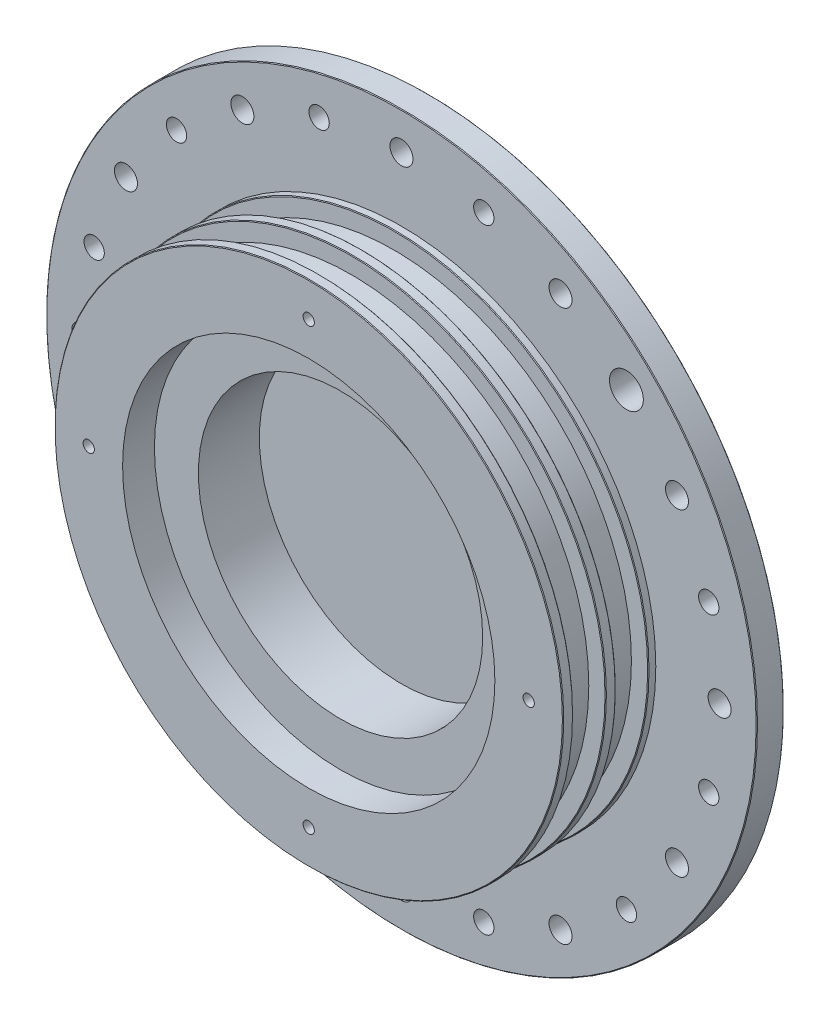
SolidWorks part; units mm, degrees
other "Marquage1"
sketch "Esquisse22" plane through (-100, 100, -114.225) normal (-0.6969, 0.6451, 0.3132) x (0.5706, 0.7634, -0.3027)
sketch "Esquisse26" plane through (-110, 110, -114.225) normal (-0.6969, 0.6451, 0.3132) x (0.5706, 0.7634, -0.3027)
sketch "Esquisse28" plane through (-110, 110, -114.225) normal (-0.6969, 0.6451, 0.3132) x (0.5706, 0.7634, -0.3027)
sketch "Esquisse31" plane through (-110, 110, -114.225) normal (-0.6969, 0.6451, 0.3132) x (0.5706, 0.7634, -0.3027)
sketch "Esquisse32" plane through (-100, 100, -114.225) normal (-0.6969, 0.6451, 0.3132) x (0.5706, 0.7634, -0.3027)
material "AISI 316 Barre d'acier inoxydable recuit (SS)"
ref_plane "Plan de face" through (0, 0, 0) normal (0, 0, 1) x (1, 0, 0)
ref_plane "Plan de dessus" through (0, 0, 0) normal (0, 1, 0) x (1, 0, 0)
ref_plane "Plan de droite" through (0, 0, 0) normal (1, 0, 0) x (0, 0, -1)
sketch "Esquisse1" plane through (0, 0, 0) normal (0, 1, 0) x (1, 0, 0)
  line L0 (87.5, 35.4) -> (0, 35.4)
  line L1 (0, 35.4) -> (0, 0)
  line L2 (0, 0) -> (75.15, 0)
  line L3 (75.15, 0) -> (75.15, 3)
  line L4 (75.15, 3) -> (70.15, 3)
  line L5 (70.15, 3) -> (70.15, 12.6)
  line L6 (70.15, 12.6) -> (75.15, 12.6)
  line L7 (75.15, 12.6) -> (75.15, 15.6)
  line L8 (75.15, 15.6) -> (70.15, 15.6)
  line L9 (70.15, 15.6) -> (70.15, 25.2)
  line L10 (70.15, 25.2) -> (75.15, 25.2)
  line L11 (75.15, 25.2) -> (75.15, 27.4)
  line L12 (75.15, 27.4) -> (87.5, 27.4)
  line L13 (87.5, 27.4) -> (87.5, 35.4)
  line L14 (0, 35.4) -> (0, 0) construction
  dimension "D1" = 8
  dimension "D2" = 2.2
  dimension "D3" = 9.6
  dimension "D4" = 3
  dimension "D5" = 9.6
  dimension "D6" = 3
  dimension "D7" = 5
  dimension "D8" = 75.15
  dimension "D9" = 87.5
revolve "Révolution1" add sketch "Esquisse1" angle 360 about L14 reverse direction yes
hole_wizard "Diamètre du perçage Ø9.0 (9)1" positions "Esquisse3" profile "Esquisse2" hole size "Ø9.0" standard "Ansi Metric"
sketch "Esquisse3" plane through (0, 0, -27.4) normal (0, 0, 1) x (1, 0, 0)
  point P0 (-87.5, 0)
  point P1 (0, 87.5)
  point P2 (0, -87.5)
  point P3 (87.5, 0)
sketch "Esquisse2" plane through (-87.5, 0, -27.4) normal (1, 0, 0) x (0, -1, 0)
  line L0 (0, 0) -> (0, 3)
  line L1 (0, 3) -> (4.5, 3)
  line L2 (4.5, 3) -> (4.5, 0)
  line L5 (4.5, 0) -> (0, 0)
  line L10 (0, 3) -> (-4.5, 3) construction
  line L11 (0, -6.35) -> (0, 107.95) construction
  dimension "Diamètre du perçage" = 9
  dimension "Profondeur du perçage" = 3
  dimension "Angle de pointe" = 180
hole_wizard "Dégagement M31" positions "Esquisse5" profile "Esquisse4" hole size "M3" standard "Ansi Metric"
sketch "Esquisse5" plane through (0, 0, 0) normal (0, 0, 1) x (1, 0, 0)
  point P0 (-65, 0)
  point P1 (65, 0)
  point P2 (0, 65)
  point P3 (0, -65)
sketch "Esquisse4" plane through (-65, 0, 0) normal (1, 0, 0) x (0, -1, 0)
  line L0 (0, 0) -> (0, 17.001)
  line L1 (0, 17.001) -> (1.666, 16)
  line L2 (1.666, 16) -> (1.666, 0)
  line L5 (1.666, 0) -> (0, 0)
  line L10 (0, 17.001) -> (-1.666, 16) construction
  line L11 (0, -6.35) -> (0, 107.95) construction
  dimension "Diamètre du perçage" = 3.332
  dimension "Profondeur du perçage" = 16
  dimension "Angle de pointe" = 118
hole_wizard "Dégagement M1001" positions "Esquisse7" profile "Esquisse6" hole size "M100" standard "Ansi Metric"
sketch "Esquisse7" plane through (0, 0, 0) normal (0, 0, 1) x (1, 0, 0)
  point P0 (0, 0)
sketch "Esquisse6" plane through (0, 0, 0) normal (1, 0, 0) x (0, -1, 0)
  line L0 (0, 0) -> (0, 27.4)
  line L1 (0, 27.4) -> (55, 27.4)
  line L2 (55, 27.4) -> (55, 0)
  line L5 (55, 0) -> (0, 0)
  line L10 (0, 27.4) -> (-55, 27.4) construction
  line L11 (0, -6.35) -> (0, 107.95) construction
  dimension "Diamètre du perçage" = 110
  dimension "Profondeur du perçage" = 27.4
  dimension "Angle de pointe" = 180
sketch "Esquisse8" plane through (0, 0, -35.4) normal (0, 0, -1) x (-1, 0, 0)
  line L0 (0, 0) -> (0, -108.9201) construction
  circle A0 centre (0, 0) radius 108.9201 construction
  circle A1 centre (0, 0) radius 105
  circle A2 centre (0, 0) radius 77.5
  circle A3 centre (0, 0) radius 87.5 construction
  dimension "D2" = 10
  dimension "D1" = 210
extrude "Boss.-Extru.1" add sketch "Esquisse8" against normal blind 8
ref_plane "Plan1" through (0, -105, 0) normal (0, -1, 0) x (-1, 0, 0)
sketch "Esquisse9" plane through (0, 0, -35.4) normal (0, 0, 1) x (1, 0, 0)
  line L0 (0, -50) -> (0, 0) construction
  circle A0 centre (0, -50) radius 3.4
  circle A17 centre (0, -94) radius 3.4
  circle A18 centre (-25, -43.3013) radius 3.4
  circle A19 centre (-47, -81.4064) radius 3.4
  circle A20 centre (-43.3013, -25) radius 3.4
  circle A21 centre (-81.4064, -47) radius 3.4
  circle A22 centre (-50, 0) radius 3.4
  circle A23 centre (-94, 0) radius 3.4
  circle A24 centre (-43.3013, 25) radius 3.4
  circle A25 centre (-81.4064, 47) radius 3.4
  circle A26 centre (-25, 43.3013) radius 3.4
  circle A27 centre (-47, 81.4064) radius 3.4
  circle A28 centre (0, 50) radius 3.4
  circle A29 centre (0, 94) radius 3.4
  circle A30 centre (25, 43.3013) radius 3.4
  circle A31 centre (47, 81.4064) radius 3.4
  circle A32 centre (43.3013, 25) radius 3.4
  circle A33 centre (81.4064, 47) radius 3.4
  circle A34 centre (50, 0) radius 3.4
  circle A35 centre (94, 0) radius 3.4
  circle A36 centre (43.3013, -25) radius 3.4
  circle A37 centre (81.4064, -47) radius 3.4
  circle A38 centre (25, -43.3013) radius 3.4
  circle A39 centre (47, -81.4064) radius 3.4
  point P17 (0, 0)
  point P28 (0, 0)
  point P31 (0, 0)
  point P55 (0, 0)
  dimension "D1" = 6.8
  dimension "D3" = 94
  dimension "D2" = 50
extrude "Enlèv. mat.-Extru.1" cut sketch "Esquisse9" along normal blind 20
sketch "Esquisse24" plane through (0, 0, -35.4) normal (0, 0, -1) x (-1, 0, 0)
  line L0 (28.0621, 104.7291) -> (0, 0) construction
  line L1 (-54.2118, 93.8976) -> (0, 0) construction
  line L2 (0, 0) -> (0, 94) construction
  line L3 (0, 0) -> (-66.468, 66.468) construction
  circle A0 centre (-47, 81.4064) radius 5 construction
  circle A1 centre (24.329, 90.797) radius 3
  circle A2 centre (66.468, 66.468) radius 3
  circle A3 centre (90.797, 24.329) radius 3
  circle A4 centre (90.797, -24.329) radius 3
  circle A5 centre (-14, 24.2487) radius 5.1
  circle A6 centre (7.2469, 27.0459) radius 5.1
  circle A7 centre (24.2487, 14) radius 5.1
  circle A8 centre (27.0459, -7.2469) radius 5.1
  circle A9 centre (14, -24.2487) radius 5.1
  circle A10 centre (-7.2469, -27.0459) radius 5.1
  circle A11 centre (-24.2487, -14) radius 5.1
  circle A12 centre (-27.0459, 7.2469) radius 5.1
  circle A13 centre (-66.468, 66.468) radius 5
  circle A14 centre (66.468, -66.468) radius 3
  circle A15 centre (24.329, -90.797) radius 3
  circle A16 centre (-24.329, -90.797) radius 3
  circle A17 centre (-66.468, -66.468) radius 3
  circle A18 centre (-90.797, -24.329) radius 3
  circle A19 centre (-90.797, 24.329) radius 3
  circle A20 centre (-66.468, 66.468) radius 3 construction
  circle A21 centre (-24.329, 90.797) radius 3
  circle A22 centre (0, 0) radius 82.55 construction
  circle A23 centre (-66.468, 66.468) radius 8 construction
  circle A24 centre (0, 0) radius 5.1
  point P19 (0, 0)
  point P36 (0, 0)
  dimension "D1" = 6
  dimension "D3" = 10
  dimension "D6" = 10.2
  dimension "D11" = 15
  dimension "D12" = 10
  dimension "D14" = 165.1
  dimension "D15" = 16
  dimension "D2" = 94
  dimension "D4" = 94
  dimension "D7" = 28
  dimension "D9" = 45
  dimension "D10" = 15
  dimension "D13" = 94
  dimension "D5" = 12
  dimension "D8" = 8
extrude "Enlèv. mat.-Extru.15" cut sketch "Esquisse24" against normal through all and the other way through all
chamfer "Chanfrein1" distance 0.2 angle 45 7 edges at (75.15, 0, -25.2) (75.15, 0, -3) (75.15, 0, -12.6) (75.15, 0, -15.6) (-105, 0, -35.4) (-105, 0, -27.4) (75.15, 0, 0)
sketch "Esquisse25" plane through (0, 0, -35.4) normal (0, 0, -1) x (-1, 0, 0)
  line L4 (0, 0) -> (-27.0459, 7.2469) construction
  line L5 (0, 0) -> (-50, 0) construction
  line L8 (-10.1, 3.1378) -> (-10.1, -3.1378)
  line L13 (10.1, 3.1378) -> (10.1, -3.1378)
  arc A1 (-10.1, 4.6043) -> (10.1, 4.6043) centre (0, 0) cw construction
  arc A2 (10.1, -4.6043) -> (-10.1, -4.6043) centre (0, 0) cw construction
  arc A3 (10.1, 3.1378) -> (9.4049, 5.8956) centre (7.191, 3.8711) ccw
  arc A4 (-10.1, 3.1378) -> (-9.4049, 5.8956) centre (-7.191, 3.8711) cw
  arc A5 (10.1, -3.1378) -> (9.4049, -5.8956) centre (7.191, -3.8711) cw
  arc A6 (-10.1, -3.1378) -> (-9.4049, -5.8956) centre (-7.191, -3.8711) ccw
  arc A7 (-9.4049, 5.8956) -> (9.4049, 5.8956) centre (0, 0) cw
  arc A8 (-9.4049, -5.8956) -> (9.4049, -5.8956) centre (0, 0) ccw
  point P5 (0, 0)
  point P19 (10.1, 4.6043)
  line B0 (-24.9287, -1.7061) -> (-33.3561, 0.552) construction
  line B1 (-33.3561, 0.552) -> (-29.1632, 16.2) construction
  line B2 (-29.1632, 16.2) -> (-20.7358, 13.9419) construction
  line B3 (-20.7358, 13.9419) -> (-24.9287, -1.7061) construction
  line B4 (-22.8322, 6.1179) -> (-31.2596, 8.376) construction
  line B5 (-27.0459, 7.2469) -> (-29.1424, -0.5771) construction
  line B6 (-22.5347, 14.4239) -> (-27.3643, 15.718)
  line B7 (-26.7275, -1.2241) -> (-31.5572, 0.07)
  arc B8 (-33.3561, 0.552) -> (-29.1632, 16.2) centre (-27.0459, 7.2469) cw construction
  arc B9 (-24.9287, -1.7061) -> (-20.7358, 13.9419) centre (-27.0459, 7.2469) ccw construction
  arc B10 (-22.8033, -0.9164) -> (-19.29, 12.1953) centre (-27.0459, 7.2469) ccw
  arc B11 (-19.29, 12.1953) -> (-19.4952, 12.5745) centre (-16.7609, 13.8089) cw
  arc B12 (-19.4952, 12.5745) -> (-21.9939, 14.3309) centre (-22.2295, 11.3402) ccw
  arc B13 (-21.9939, 14.3309) -> (-22.5347, 14.4239) centre (-21.7582, 17.3217) cw
  arc B14 (-27.8791, 15.9079) -> (-27.3643, 15.718) centre (-26.5878, 18.6158) ccw
  arc B15 (-30.9212, 15.6361) -> (-27.8791, 15.9079) centre (-29.1704, 13.2) cw
  arc B16 (-31.2885, 15.4103) -> (-30.9212, 15.6361) centre (-32.672, 18.0722) ccw
  arc B17 (-34.8018, 2.2986) -> (-31.2885, 15.4103) centre (-27.0459, 7.2469) cw
  arc B18 (-34.8018, 2.2986) -> (-34.5966, 1.9193) centre (-37.3309, 0.685) cw
  arc B19 (-34.5966, 1.9193) -> (-32.098, 0.1629) centre (-31.8623, 3.1537) ccw
  arc B20 (-32.098, 0.1629) -> (-31.5572, 0.07) centre (-32.3336, -2.8278) cw
  arc B21 (-26.2127, -1.414) -> (-26.7275, -1.2241) centre (-27.504, -4.1219) ccw
  arc B22 (-23.1707, -1.1423) -> (-26.2127, -1.414) centre (-24.9215, 1.2939) cw
  arc B23 (-22.8033, -0.9164) -> (-23.1707, -1.1423) centre (-21.4198, -3.5784) ccw
  line B24 (-5.7352, 26.1336) -> (-8.2352, 30.4638)
  line B25 (-19.7648, 18.0336) -> (-22.2648, 22.3638)
  arc B26 (-16.7724, 15.4764) -> (-5.0167, 22.2635) centre (-14, 24.2487) ccw
  arc B27 (-5.0167, 22.2635) -> (-4.8937, 22.6768) centre (-2.0874, 21.6161) cw
  arc B28 (-4.8937, 22.6768) -> (-5.4185, 25.6855) centre (-7.6999, 23.7374) ccw
  arc B29 (-5.4185, 25.6855) -> (-5.7352, 26.1336) centre (-3.1371, 27.6336) cw
  arc B30 (-8.4649, 30.9621) -> (-8.2352, 30.4638) centre (-5.6371, 31.9638) ccw
  arc B31 (-10.8082, 32.921) -> (-8.4649, 30.9621) centre (-11.2928, 29.9604) cw
  arc B32 (-11.2276, 33.0211) -> (-10.8082, 32.921) centre (-10.3236, 35.8816) ccw
  arc B33 (-22.9833, 26.2339) -> (-11.2276, 33.0211) centre (-14, 24.2487) cw
  arc B34 (-22.9833, 26.2339) -> (-23.1063, 25.8207) centre (-25.9126, 26.8813) cw
  arc B35 (-23.1063, 25.8207) -> (-22.5815, 22.8119) centre (-20.3001, 24.76) ccw
  arc B36 (-22.5815, 22.8119) -> (-22.2648, 22.3638) centre (-24.8629, 20.8638) cw
  arc B37 (-19.5351, 17.5353) -> (-19.7648, 18.0336) centre (-22.3629, 16.5336) ccw
  arc B38 (-17.1918, 15.5764) -> (-19.5351, 17.5353) centre (-16.7072, 18.537) cw
  arc B39 (-16.7724, 15.4764) -> (-17.1918, 15.5764) centre (-17.6764, 12.6158) ccw
  line B40 (14.4239, 22.5347) -> (15.718, 27.3643)
  line B41 (-1.2241, 26.7275) -> (0.07, 31.5572)
  arc B42 (-0.9164, 22.8033) -> (12.1953, 19.29) centre (7.2469, 27.0459) ccw
  arc B43 (12.1953, 19.29) -> (12.5745, 19.4952) centre (13.8089, 16.7609) cw
  arc B44 (12.5745, 19.4952) -> (14.3309, 21.9939) centre (11.3402, 22.2295) ccw
  arc B45 (14.3309, 21.9939) -> (14.4239, 22.5347) centre (17.3217, 21.7582) cw
  arc B46 (15.9079, 27.8791) -> (15.718, 27.3643) centre (18.6158, 26.5878) ccw
  arc B47 (15.6361, 30.9212) -> (15.9079, 27.8791) centre (13.2, 29.1704) cw
  arc B48 (15.4103, 31.2885) -> (15.6361, 30.9212) centre (18.0722, 32.672) ccw
  arc B49 (2.2986, 34.8018) -> (15.4103, 31.2885) centre (7.2469, 27.0459) cw
  arc B50 (2.2986, 34.8018) -> (1.9193, 34.5966) centre (0.685, 37.3309) cw
  arc B51 (1.9193, 34.5966) -> (0.1629, 32.098) centre (3.1537, 31.8623) ccw
  arc B52 (0.1629, 32.098) -> (0.07, 31.5572) centre (-2.8278, 32.3336) cw
  arc B53 (-1.414, 26.2127) -> (-1.2241, 26.7275) centre (-4.1219, 27.504) ccw
  arc B54 (-1.1423, 23.1707) -> (-1.414, 26.2127) centre (1.2939, 24.9215) cw
  arc B55 (-0.9164, 22.8033) -> (-1.1423, 23.1707) centre (-3.5784, 21.4198) ccw
  line B56 (26.1336, 5.7352) -> (30.4638, 8.2352)
  line B57 (18.0336, 19.7648) -> (22.3638, 22.2648)
  arc B58 (15.4764, 16.7724) -> (22.2635, 5.0167) centre (24.2487, 14) ccw
  arc B59 (22.2635, 5.0167) -> (22.6768, 4.8937) centre (21.6161, 2.0874) cw
  arc B60 (22.6768, 4.8937) -> (25.6855, 5.4185) centre (23.7374, 7.6999) ccw
  arc B61 (25.6855, 5.4185) -> (26.1336, 5.7352) centre (27.6336, 3.1371) cw
  arc B62 (30.9621, 8.4649) -> (30.4638, 8.2352) centre (31.9638, 5.6371) ccw
  arc B63 (32.921, 10.8082) -> (30.9621, 8.4649) centre (29.9604, 11.2928) cw
  arc B64 (33.0211, 11.2276) -> (32.921, 10.8082) centre (35.8816, 10.3236) ccw
  arc B65 (26.2339, 22.9833) -> (33.0211, 11.2276) centre (24.2487, 14) cw
  arc B66 (26.2339, 22.9833) -> (25.8207, 23.1063) centre (26.8813, 25.9126) cw
  arc B67 (25.8207, 23.1063) -> (22.8119, 22.5815) centre (24.76, 20.3001) ccw
  arc B68 (22.8119, 22.5815) -> (22.3638, 22.2648) centre (20.8638, 24.8629) cw
  arc B69 (17.5353, 19.5351) -> (18.0336, 19.7648) centre (16.5336, 22.3629) ccw
  arc B70 (15.5764, 17.1918) -> (17.5353, 19.5351) centre (18.537, 16.7072) cw
  arc B71 (15.4764, 16.7724) -> (15.5764, 17.1918) centre (12.6158, 17.6764) ccw
  line B72 (22.5347, -14.4239) -> (27.3643, -15.718)
  line B73 (26.7275, 1.2241) -> (31.5572, -0.07)
  arc B74 (22.8033, 0.9164) -> (19.29, -12.1953) centre (27.0459, -7.2469) ccw
  arc B75 (19.29, -12.1953) -> (19.4952, -12.5745) centre (16.7609, -13.8089) cw
  arc B76 (19.4952, -12.5745) -> (21.9939, -14.3309) centre (22.2295, -11.3402) ccw
  arc B77 (21.9939, -14.3309) -> (22.5347, -14.4239) centre (21.7582, -17.3217) cw
  arc B78 (27.8791, -15.9079) -> (27.3643, -15.718) centre (26.5878, -18.6158) ccw
  arc B79 (30.9212, -15.6361) -> (27.8791, -15.9079) centre (29.1704, -13.2) cw
  arc B80 (31.2885, -15.4103) -> (30.9212, -15.6361) centre (32.672, -18.0722) ccw
  arc B81 (34.8018, -2.2986) -> (31.2885, -15.4103) centre (27.0459, -7.2469) cw
  arc B82 (34.8018, -2.2986) -> (34.5966, -1.9193) centre (37.3309, -0.685) cw
  arc B83 (34.5966, -1.9193) -> (32.098, -0.1629) centre (31.8623, -3.1537) ccw
  arc B84 (32.098, -0.1629) -> (31.5572, -0.07) centre (32.3336, 2.8278) cw
  arc B85 (26.2127, 1.414) -> (26.7275, 1.2241) centre (27.504, 4.1219) ccw
  arc B86 (23.1707, 1.1423) -> (26.2127, 1.414) centre (24.9215, -1.2939) cw
  arc B87 (22.8033, 0.9164) -> (23.1707, 1.1423) centre (21.4198, 3.5784) ccw
  line B88 (5.7352, -26.1336) -> (8.2352, -30.4638)
  line B89 (19.7648, -18.0336) -> (22.2648, -22.3638)
  arc B90 (16.7724, -15.4764) -> (5.0167, -22.2635) centre (14, -24.2487) ccw
  arc B91 (5.0167, -22.2635) -> (4.8937, -22.6768) centre (2.0874, -21.6161) cw
  arc B92 (4.8937, -22.6768) -> (5.4185, -25.6855) centre (7.6999, -23.7374) ccw
  arc B93 (5.4185, -25.6855) -> (5.7352, -26.1336) centre (3.1371, -27.6336) cw
  arc B94 (8.4649, -30.9621) -> (8.2352, -30.4638) centre (5.6371, -31.9638) ccw
  arc B95 (10.8082, -32.921) -> (8.4649, -30.9621) centre (11.2928, -29.9604) cw
  arc B96 (11.2276, -33.0211) -> (10.8082, -32.921) centre (10.3236, -35.8816) ccw
  arc B97 (22.9833, -26.2339) -> (11.2276, -33.0211) centre (14, -24.2487) cw
  arc B98 (22.9833, -26.2339) -> (23.1063, -25.8207) centre (25.9126, -26.8813) cw
  arc B99 (23.1063, -25.8207) -> (22.5815, -22.8119) centre (20.3001, -24.76) ccw
  arc B100 (22.5815, -22.8119) -> (22.2648, -22.3638) centre (24.8629, -20.8638) cw
  arc B101 (19.5351, -17.5353) -> (19.7648, -18.0336) centre (22.3629, -16.5336) ccw
  arc B102 (17.1918, -15.5764) -> (19.5351, -17.5353) centre (16.7072, -18.537) cw
  arc B103 (16.7724, -15.4764) -> (17.1918, -15.5764) centre (17.6764, -12.6158) ccw
  line B104 (-14.4239, -22.5347) -> (-15.718, -27.3643)
  line B105 (1.2241, -26.7275) -> (-0.07, -31.5572)
  arc B106 (0.9164, -22.8033) -> (-12.1953, -19.29) centre (-7.2469, -27.0459) ccw
  arc B107 (-12.1953, -19.29) -> (-12.5745, -19.4952) centre (-13.8089, -16.7609) cw
  arc B108 (-12.5745, -19.4952) -> (-14.3309, -21.9939) centre (-11.3402, -22.2295) ccw
  arc B109 (-14.3309, -21.9939) -> (-14.4239, -22.5347) centre (-17.3217, -21.7582) cw
  arc B110 (-15.9079, -27.8791) -> (-15.718, -27.3643) centre (-18.6158, -26.5878) ccw
  arc B111 (-15.6361, -30.9212) -> (-15.9079, -27.8791) centre (-13.2, -29.1704) cw
  arc B112 (-15.4103, -31.2885) -> (-15.6361, -30.9212) centre (-18.0722, -32.672) ccw
  arc B113 (-2.2986, -34.8018) -> (-15.4103, -31.2885) centre (-7.2469, -27.0459) cw
  arc B114 (-2.2986, -34.8018) -> (-1.9193, -34.5966) centre (-0.685, -37.3309) cw
  arc B115 (-1.9193, -34.5966) -> (-0.1629, -32.098) centre (-3.1537, -31.8623) ccw
  arc B116 (-0.1629, -32.098) -> (-0.07, -31.5572) centre (2.8278, -32.3336) cw
  arc B117 (1.414, -26.2127) -> (1.2241, -26.7275) centre (4.1219, -27.504) ccw
  arc B118 (1.1423, -23.1707) -> (1.414, -26.2127) centre (-1.2939, -24.9215) cw
  arc B119 (0.9164, -22.8033) -> (1.1423, -23.1707) centre (3.5784, -21.4198) ccw
  line B120 (-26.1336, -5.7352) -> (-30.4638, -8.2352)
  line B121 (-18.0336, -19.7648) -> (-22.3638, -22.2648)
  arc B122 (-15.4764, -16.7724) -> (-22.2635, -5.0167) centre (-24.2487, -14) ccw
  arc B123 (-22.2635, -5.0167) -> (-22.6768, -4.8937) centre (-21.6161, -2.0874) cw
  arc B124 (-22.6768, -4.8937) -> (-25.6855, -5.4185) centre (-23.7374, -7.6999) ccw
  arc B125 (-25.6855, -5.4185) -> (-26.1336, -5.7352) centre (-27.6336, -3.1371) cw
  arc B126 (-30.9621, -8.4649) -> (-30.4638, -8.2352) centre (-31.9638, -5.6371) ccw
  arc B127 (-32.921, -10.8082) -> (-30.9621, -8.4649) centre (-29.9604, -11.2928) cw
  arc B128 (-33.0211, -11.2276) -> (-32.921, -10.8082) centre (-35.8816, -10.3236) ccw
  arc B129 (-26.2339, -22.9833) -> (-33.0211, -11.2276) centre (-24.2487, -14) cw
  arc B130 (-26.2339, -22.9833) -> (-25.8207, -23.1063) centre (-26.8813, -25.9126) cw
  arc B131 (-25.8207, -23.1063) -> (-22.8119, -22.5815) centre (-24.76, -20.3001) ccw
  arc B132 (-22.8119, -22.5815) -> (-22.3638, -22.2648) centre (-20.8638, -24.8629) cw
  arc B133 (-17.5353, -19.5351) -> (-18.0336, -19.7648) centre (-16.5336, -22.3629) ccw
  arc B134 (-15.5764, -17.1918) -> (-17.5353, -19.5351) centre (-18.537, -16.7072) cw
  arc B135 (-15.4764, -16.7724) -> (-15.5764, -17.1918) centre (-12.6158, -17.6764) ccw
  line B136 (0, 0) -> (0, 11.1) construction
  line B137 (10.1, 4.6043) -> (10.1, -4.6043) construction
  line B138 (-10.1, 4.6043) -> (-10.1, -4.6043) construction
  circle B139 centre (0, 0) radius 11.1 construction
  dimension "D1" = 28
  dimension "D3" = 8
  dimension "D4" = 3
  dimension "D5" = 14.382
  dimension "D2" = 15
sketch_block_instance "Bloc1-1"
sketch_block "Bloc1" parameters "D2"=9.2, "D3"=3, "D1"=16.2, "D4"=2.5, "D5"=0.7323
sketch_block_instance "Bloc1-2"
sketch_block_instance "Bloc1-3"
sketch_block_instance "Bloc1-4"
sketch_block_instance "Bloc1-5"
sketch_block_instance "Bloc1-6"
sketch_block_instance "Bloc1-7"
sketch_block_instance "Bloc1-8"
sketch_block_instance "Bloc2-1"
sketch_block "Bloc2" parameters "D1"=20.2
sketch_block_instance "Bloc2-2"
extrude "Enlèv. mat.-Extru.18" cut sketch "Esquisse25" against normal blind 2
sketch "Esquisse35" plane through (0, 0, -27.4) normal (0, 0, 1) x (1, 0, 0)
  circle A0 centre (0, 0) radius 55
  circle A1 centre (0, 0) radius 42
  circle A4 centre (0, 0) radius 55 construction
  dimension "D1" = 84
extrude "Boss.-Extru.4" add sketch "Esquisse35" along normal blind 18
sketch "Esquisse36" plane through (0, 0, -27.4) normal (0, 0, 1) x (1, 0, 0)
  circle A0 centre (-27.0459, -7.2469) radius 5.1
  circle A1 centre (-27.0459, -7.2469) radius 5.1 construction
  circle A2 centre (-24.2487, 14) radius 5.1
  circle A3 centre (-7.2469, 27.0459) radius 5.1
  circle A4 centre (14, 24.2487) radius 5.1
  circle A5 centre (27.0459, 7.2469) radius 5.1
  circle A6 centre (24.2487, -14) radius 5.1
  circle A7 centre (7.2469, -27.0459) radius 5.1
  circle A8 centre (-14, -24.2487) radius 5.1
  circle A9 centre (0, 0) radius 5.1
  circle A11 centre (0, 0) radius 5.1 construction
  point P14 (0, 0)
  dimension "D1" = 8
extrude "Boss.-Extru.5" add sketch "Esquisse36" against normal blind 5
extrude "Enlèv. mat.-Extru.20" cut sketch "Esquisse9<2>" along normal blind 20
sketch "Esquisse9<2>" plane through (0, 0, -35.4) normal (0, 0, 1) x (1, 0, 0) same geometry as "Esquisse9"
sketch "Esquisse37" plane through (0, 0, -35.4) normal (0, 0, -1) x (-1, 0, 0)
  point P0 (-14, 24.2487)
  point P1 (14, -24.2487)
ref_plane "Plan2" through (0, 0, 0) normal (-0.866, 0.5, 0) x (0, 0, 1)
sketch "Esquisse38" plane through (0, 0, 0) normal (-0.866, 0.5, 0) x (0, 0, 1)
  line L0 (-35.4, 28) -> (-30.4, 28)
  line L1 (-30.4, 28) -> (-32.4, 33.1)
  line L2 (-32.4, 33.1) -> (-35.4, 33.1)
  line L4 (-35.4, 33.1) -> (-35.4, 28)
  dimension "D1" = 5.1
  dimension "D2" = 5
  dimension "D3" = 3
revolve "Enlèvement de matière-Révolution4" cut sketch "Esquisse38" angle 360 about L0
pattern_circular "Répétition circulaire1" count 8 over 360 about axis through (0, 0, -32.4) along (0, 0, -1) of "Enlèvement de matière-Révolution4"
sketch "Esquisse39" plane through (0, 0, 0) normal (-0.866, 0.5, 0) x (0, 0, 1)
  line L0 (0, 0) -> (-35.4, 0) construction
  line L1 (-35.4, 104.8) -> (-35.4, -104.8) construction
  line L2 (-35.4, 0) -> (-35.4, 7.1)
  line L3 (-35.4, 7.1) -> (-32.4, 7.1)
  line L4 (-32.4, 7.1) -> (-30.4, 0)
  line L5 (-30.4, 0) -> (-35.4, 0)
  dimension "D1" = 5
  dimension "D2" = 3
  dimension "D3" = 7.1
revolve "Enlèvement de matière-Révolution5" cut sketch "Esquisse39" angle 360 about L0
equation "\"_à\"=76.5769"
